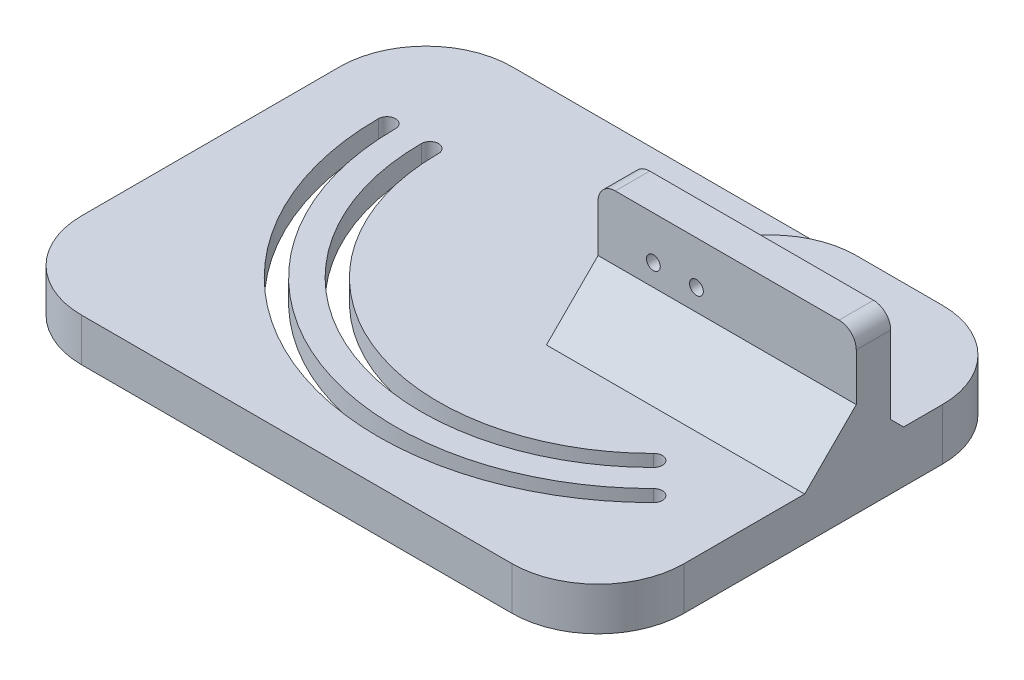
SolidWorks part; units mm, degrees
ref_plane "Front Plane" through (0, 0, 0) normal (0, 0, 1) x (1, 0, 0)
ref_plane "Top Plane" through (0, 0, 0) normal (0, 1, 0) x (1, 0, 0)
ref_plane "Right Plane" through (0, 0, 0) normal (1, 0, 0) x (0, 0, -1)
sketch "Sketch1" plane through (0, 0, 0) normal (0, 1, 0) x (1, 0, 0)
  line L1 (0, 0) -> (170, 0)
  line L2 (0, 0) -> (0, 120)
  line L3 (0, 120) -> (170, 120)
  line L4 (170, 0) -> (170, 120)
extrude "Boss-Extrude1" add sketch "Sketch1" along normal blind 10
sketch "Sketch2" plane through (0, 10, 0) normal (0, 1, 0) x (1, 0, 0)
  line L0 (170, 120) -> (170, 80)
  line L1 (170, 0) -> (170, 120) construction
  line L2 (170, 80) -> (110, 80)
  line L3 (110, 80) -> (110, 120)
  line L4 (170, 120) -> (0, 120) construction
  line L5 (110, 120) -> (170, 120)
extrude "Boss-Extrude2" add sketch "Sketch2" along normal blind 2
sketch "Sketch3" plane through (0, 12, 0) normal (0, 1, 0) x (1, 0, 0)
  line L6 (170, 80) -> (110, 80)
  line L7 (110, 80) -> (110, 88)
  line L8 (110, 120) -> (110, 80) construction
  line L9 (110, 88) -> (170, 88)
  line L10 (170, 80) -> (170, 120) construction
  line L11 (170, 88) -> (170, 80)
extrude "Boss-Extrude3" add sketch "Sketch3" along normal blind 25
sketch "Sketch4" plane through (0, 0, -88) normal (0, 0, -1) x (-1, 0, 0)
  line L0 (-132.8549, 27) -> (-122.8549, 27) construction
  line L2 (-170, 37) -> (-110, 37) construction
  circle A1 centre (-132.8549, 27) radius 1.6
  circle A2 centre (-122.8549, 27) radius 1.6
  dimension "D1" = 10
extrude "Cut-Extrude1" cut sketch "Sketch4" against normal blind 10 contours A1 | A2 region at (132.8549, 27, -88)
sketch "Sketch5" plane through (0, 10, 0) normal (0, 1, 0) x (1, 0, 0)
  arc A16 (44.9348, 94) -> (154.1897, 48.7452) centre (108.9348, 94) ccw
  arc A17 (48.9348, 94) -> (151.3612, 51.5736) centre (108.9348, 94) ccw
  arc A18 (48.9348, 94) -> (44.9348, 94) centre (46.9348, 94) ccw
  arc A19 (154.1897, 48.7452) -> (151.3612, 51.5736) centre (152.7755, 50.1594) ccw
  arc A21 (58.9348, 94) -> (144.2902, 58.6447) centre (108.9348, 94) ccw
  arc A22 (54.9348, 94) -> (147.1186, 55.8162) centre (108.9348, 94) ccw
  arc A23 (58.9348, 94) -> (54.9348, 94) centre (56.9348, 94) ccw
  arc A24 (147.1186, 55.8162) -> (144.2902, 58.6447) centre (145.7044, 57.2304) ccw
extrude "Cut-Extrude2" cut sketch "Sketch5" against normal blind 36 contours A21 A24 A22 A23 | A17 A19 A16 A18
chamfer "Chamfer1" distance 12 angle 45 1 edges at (140, 10, -80)
fillet "Fillet4" radius 4 2 edges at (170, 37, -84) (110, 37, -84)
chamfer "Chamfer2" distance 3 angle 45 1 edges at (140, 12, -88)
sketch "Sketch7" plane through (0, 0, 0) normal (0, -1, 0) x (1, 0, 0)
  arc A0 (140.7546, -62.1802) -> (63.9348, -94) centre (108.9348, -94) ccw
  arc A1 (157.7252, -45.2096) -> (39.9348, -94) centre (108.9348, -94) ccw
  arc A2 (39.9348, -94) -> (63.9348, -94) centre (51.9348, -94) ccw
  arc A3 (140.7546, -62.1802) -> (157.7252, -45.2096) centre (149.2399, -53.6949) ccw
extrude "Cut-Extrude4" cut sketch "Sketch7" against normal blind 5
sketch "Sketch8" plane through (0, 10, 0) normal (0, 1, 0) x (1, 0, 0)
  line L0 (110, 120) -> (0, 120) construction
  line L1 (0, 0) -> (30, 0)
  line L2 (0, 0) -> (0, 120)
  line L3 (0, 120) -> (30, 120)
  line L4 (30, 20) -> (30, 120)
  line L5 (170, 0) -> (170, 20)
  line L6 (170, 0) -> (170, 68) construction
  line L7 (170, 20) -> (30, 20)
  line L8 (170, 0) -> (30, 0)
extrude "Cut-Extrude5" cut sketch "Sketch8" against normal blind 19
fillet "Fillet5" radius 20 5 edges at (30, 5, -120) (170, 6, -120) (110, 11, -120) (30, 5, -20) (170, 5, -20)
